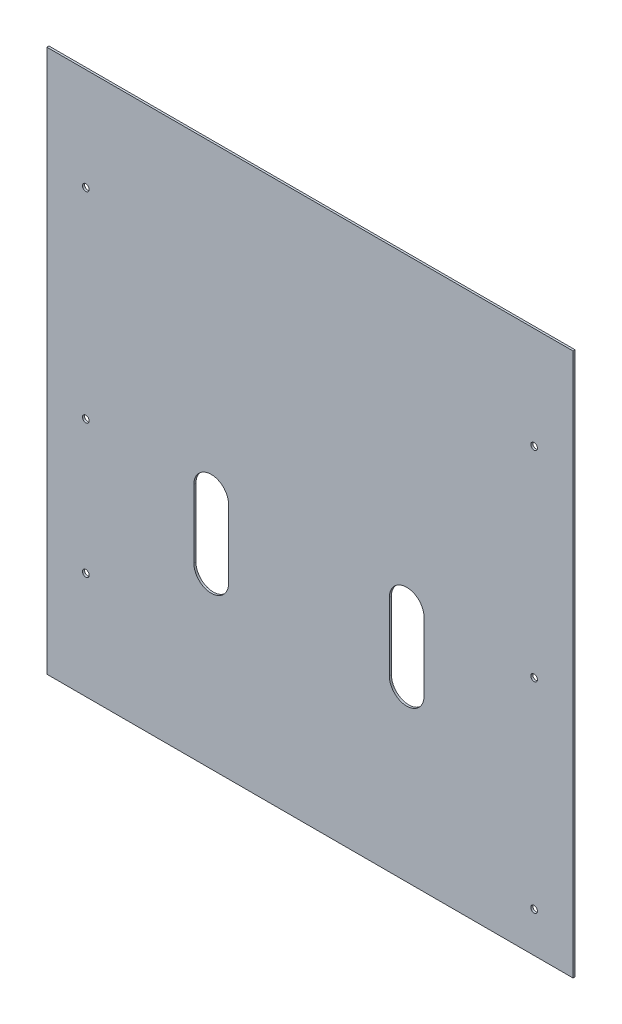
SolidWorks part; units mm, degrees
ref_plane "Front Plane" through (0, 0, 0) normal (0, 0, 1) x (1, 0, 0)
ref_plane "Top Plane" through (0, 0, 0) normal (0, 1, 0) x (1, 0, 0)
ref_plane "Right Plane" through (0, 0, 0) normal (1, 0, 0) x (0, 0, -1)
sketch "Sketch1" plane through (0, 0, 0) normal (0, 0, -1) x (1, 0, 0)
  line L1 (-203.2, 237) -> (-6.35, 237)
  line L2 (-203.2, 237) -> (-203.2, 33.8)
  line L3 (-203.2, 33.8) -> (-6.35, 33.8)
  line L4 (-6.35, 237) -> (-6.35, 33.8)
  dimension "D2" = 196.85
  dimension "D3" = 203.2
extrude "Boss-Extrude1" add sketch "Sketch1" along normal blind 0.7747
sketch "Sketch2" plane through (0, 0, -0.7747) normal (0, 0, -1) x (1, 0, 0)
  line L0 (-141.7213, 180) -> (-141.7213, 141.5) construction
  line L1 (-6.35, 237) -> (-203.2, 237) construction
  line L2 (-141.7213, 180) -> (-141.7213, 237) construction
  line L3 (-141.7213, 173.5) -> (-141.7213, 148) construction
  line L6 (-135.2213, 173.5) -> (-135.2213, 148)
  line L7 (-148.2213, 173.5) -> (-148.2213, 148)
  line L8 (-141.7213, 160.75) -> (-203.2, 160.75) construction
  line L9 (-203.2, 237) -> (-203.2, 33.8) construction
  line L10 (-68.5693, 180) -> (-68.5693, 141.5) construction
  line L11 (-68.5693, 180) -> (-68.5693, 237) construction
  line L12 (-68.5693, 173.5) -> (-68.5693, 148) construction
  line L15 (-141.7213, 160.75) -> (-68.5693, 160.75) construction
  line L16 (-62.0693, 173.5) -> (-62.0693, 148)
  line L17 (-75.0693, 173.5) -> (-75.0693, 148)
  arc A2 (-135.2213, 173.5) -> (-148.2213, 173.5) centre (-141.7213, 173.5) ccw
  arc A3 (-148.2213, 148) -> (-135.2213, 148) centre (-141.7213, 148) ccw
  arc A6 (-62.0693, 173.5) -> (-75.0693, 173.5) centre (-68.5693, 173.5) ccw
  arc A7 (-75.0693, 148) -> (-62.0693, 148) centre (-68.5693, 148) ccw
  point P5 (-141.7213, 160.75)
  point P18 (-68.5693, 160.75)
  dimension "D4" = 6.5
  dimension "D6" = 57
  dimension "D5" = 6.5
  dimension "D1" = 73.152
  dimension "D2" = 57
  dimension "D3" = 38.5
  dimension "D8" = 38.5
extrude "Cut-Extrude7" cut sketch "Sketch2" against normal through all
ref_plane "Plane1" through (-104.775, 0, 0) normal (1, 0, 0) x (0, 0, -1)
sketch "Sketch4" plane through (0, 0, 0) normal (0, 0, 1) x (1, 0, 0)
  line L0 (-203.2, -33.8) -> (-6.35, -33.8) construction
  line L1 (-6.35, -33.8) -> (-203.2, -33.8)
  line L2 (-6.35, -33.8) -> (-6.35, -34.4096)
  line L3 (-6.35, -34.4096) -> (-203.2, -34.4096)
  line L4 (-203.2, -33.8) -> (-203.2, -34.4096)
  line L5 (-6.35, -237) -> (-6.35, 2) construction
  line L6 (-203.2, 2) -> (-203.2, -237) construction
  dimension "D1" = 0.6096
extrude "Boss-Extrude2" add sketch "Sketch4" along normal blind 12
sketch "Sketch8" plane through (0, 0, -0.7747) normal (0, 0, -1) x (-1, 0, 0)
  circle A0 centre (185.47, -222) radius 3.75
  circle A1 centre (185.47, -197) radius 3.75
  circle A2 centre (185.47, -172) radius 3.75
  circle A3 centre (185.47, -147) radius 3.75
  circle A4 centre (185.47, -122) radius 3.75
  circle A5 centre (185.47, -97) radius 3.75
  dimension "D1" = 7.5
sketch "Sketch13" plane through (0, 0, 12) normal (0, 0, 1) x (1, 0, 0)
  line L1 (-6.35, -34.4096) -> (-203.2, -34.4096)
  line L2 (-6.35, -34.4096) -> (-6.35, -33.8)
  line L3 (-6.35, -33.8) -> (-203.2, -33.8)
  line L4 (-203.2, -34.4096) -> (-203.2, -33.8)
sketch "Sketch14" plane through (0, 0, 0) normal (0, 0, 1) x (1, 0, 0)
  line L0 (-6.35, -34.4096) -> (-6.35, -237) construction
  line L1 (-6.35, -59.904) -> (-203.2, -59.904)
  line L2 (-6.35, -59.904) -> (-6.35, -47.966)
  line L3 (-6.35, -47.966) -> (-203.2, -47.966)
  line L4 (-203.2, -59.904) -> (-203.2, -47.966)
  line L5 (-203.2, -237) -> (-203.2, -34.4096) construction
  dimension "D1" = 11.938
extrude "Boss-Extrude3" add sketch "Sketch14" against normal up to surface (0.7747 mm away) up to face at (-141.7213, -160.75, -0.7747)
extrude "Cut-Extrude9" cut sketch "Sketch13" against normal up to surface (12 mm away) up to face at (-68.5693, -160.75, 0)
hole_wizard "CSK for M3 Flat Head Machine Screw3" positions "Sketch15" profile "Sketch16" tap size "M3x0.5" standard "ANSI Metric" end condition through all
sketch "Sketch15" plane through (0, 0, 0) normal (0, 0, 1) x (1, 0, 0)
  point P18 (-188.645, -72)
  point P21 (-188.645, -222)
  point P24 (-188.645, -197)
  point P27 (-188.645, -172)
  point P30 (-188.645, -147)
  point P33 (-188.645, -122)
  point P36 (-188.645, -97)
  point P39 (-188.645, -72)
sketch "Sketch16" plane through (-188.645, -72, 0) normal (1, 0, 0) x (0, -1, 0)
  line L0 (0, 0) -> (0, 0.7747)
  line L1 (0, 0.7747) -> (1.25, 0.7747)
  line L2 (1.25, 0.7747) -> (1.25, 0)
  line L5 (1.25, 0) -> (0, 0)
  line L11 (0, -6.35) -> (0, 107.95) construction
  dimension "Thru Tap Drill Dia." = 2.5
  dimension "Thru Tap Drill Depth" = 0.7747
ref_plane "Plane2" through (-104.775, 0, 0) normal (1, 0, 0) x (0, 0, -1)
mirror "Mirror1" about plane through (-104.775, 0, 0) normal (1, 0, 0) of "CSK for M3 Flat Head Machine Screw3"
sketch "Sketch17" plane through (0, 0, -0.7747) normal (0, 0, -1) x (-1, 0, 0)
  line L0 (62.0693, -148) -> (62.0693, -173.5) construction
  point P8 (141.7213, -160.75)
  point P17 (68.5693, -160.75)
  dimension "D1" = 6.5
  dimension "D2" = 79.652
  dimension "D3" = 12.75
sketch "Sketch19" plane through (0, 0, -0.7747) normal (0, 0, -1) x (-1, 0, 0)
  line L6 (9.9285, -126.7081) -> (192.6049, -126.7081)
  line L7 (9.9285, -126.7081) -> (9.9285, -92.9669)
  line L8 (9.9285, -92.9669) -> (192.6049, -92.9669)
  line L9 (192.6049, -126.7081) -> (192.6049, -92.9669)
extrude "Boss-Extrude4" add sketch "Sketch19" against normal up to surface (0.7747 mm away) up to face at (-19.655, -222, 0)
sketch "Sketch21" plane through (0, 0, -0.7747) normal (0, 0, -1) x (-1, 0, 0)
  line L1 (174.2127, -182.0755) -> (196.9307, -182.0755)
  line L2 (13.502, -182.0755) -> (35.0408, -182.0755)
  line L3 (13.502, -182.0755) -> (13.502, -165.4323)
  line L4 (13.502, -165.4323) -> (35.0408, -165.4323)
  line L5 (35.0408, -182.0755) -> (35.0408, -165.4323)
  line L6 (174.2127, -182.0755) -> (174.2127, -159.7632)
  line L7 (174.2127, -159.7632) -> (196.9307, -159.7632)
  line L8 (196.9307, -182.0755) -> (196.9307, -159.7632)
extrude "Boss-Extrude5" add sketch "Sketch21" against normal up to surface (0.7747 mm away) up to face at (-19.655, -222, 0)
sketch "Sketch22" plane through (0, 0, 0) normal (0, 0, 1) x (1, 0, 0)
  line L1 (-182.3612, -227.9915) -> (-196.2665, -227.9915)
  line L2 (-17.4152, -202.4142) -> (-29.9248, -202.4142)
  line L3 (-17.4152, -202.4142) -> (-17.4152, -193.3386)
  line L4 (-17.4152, -193.3386) -> (-29.9248, -193.3386)
  line L5 (-29.9248, -202.4142) -> (-29.9248, -193.3386)
  line L6 (-182.3612, -227.9915) -> (-182.3612, -213.7762)
  line L7 (-182.3612, -213.7762) -> (-196.2665, -213.7762)
  line L8 (-196.2665, -227.9915) -> (-196.2665, -213.7762)
extrude "Boss-Extrude6" add sketch "Sketch22" against normal up to surface (0.7747 mm away) up to face at (-19.655, -222, -0.7747)
